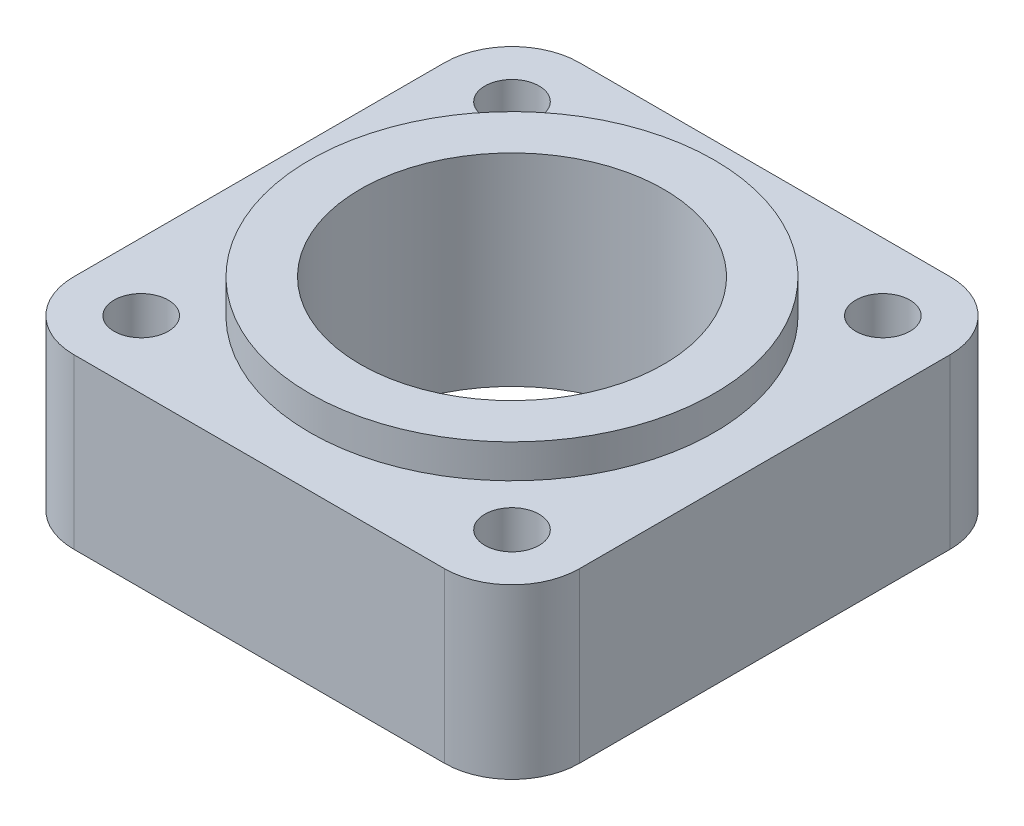
SolidWorks part; units mm, degrees
material "6061-T6 (SS)"
ref_plane "Front Plane" through (0, 0, 0) normal (0, 0, 1) x (1, 0, 0)
ref_plane "Top Plane" through (0, 0, 0) normal (0, 1, 0) x (1, 0, 0)
ref_plane "Right Plane" through (0, 0, 0) normal (1, 0, 0) x (0, 0, -1)
sketch "Sketch1" plane through (0, 0, 0) normal (0, 1, 0) x (1, 0, 0)
  line L1 (23.8125, -23.8125) -> (-23.8125, -23.8125)
  line L2 (23.8125, -23.8125) -> (23.8125, 23.8125)
  line L3 (23.8125, 23.8125) -> (-23.8125, 23.8125)
  line L4 (-23.8125, -23.8125) -> (-23.8125, 23.8125)
  line L5 (23.8125, -23.8125) -> (-23.8125, 23.8125) construction
  line L6 (23.8125, 23.8125) -> (-23.8125, -23.8125) construction
  point P0 (0, 0)
  dimension "D1" = 47.625
extrude "Boss-Extrude1" add sketch "Sketch1" along normal blind 15.875
sketch "Sketch2" plane through (0, 15.875, 0) normal (0, 1, 0) x (1, 0, 0)
  circle A0 centre (0, 0) radius 19.05
  dimension "D1" = 38.1
extrude "Boss-Extrude2" add sketch "Sketch2" along normal blind 3.175
sketch "Sketch3" plane through (0, 19.05, 0) normal (0, 1, 0) x (1, 0, 0)
  circle A0 centre (0, 0) radius 14.2875
  dimension "D1" = 28.575
extrude "Cut-Extrude1" cut sketch "Sketch3" against normal through all
hole_wizard "1/4-20 Tapped Hole1" positions "Sketch4" profile "Sketch5" tap size "1/4-20" standard "ANSI Inch" end condition through all
sketch "Sketch4" plane through (0, 15.875, 0) normal (0, 1, 0) x (1, 0, 0)
  line L0 (-23.8125, 23.8125) -> (23.8125, -23.8125) construction
  line L2 (-23.8125, -23.8125) -> (23.8125, 23.8125) construction
  point P0 (-17.4625, 17.4625)
  point P2 (17.4625, 17.4625)
  point P4 (17.4625, -17.4625)
  point P6 (-17.4625, -17.4625)
  dimension "D1" = 34.925
sketch "Sketch5" plane through (-17.4625, 15.875, -17.4625) normal (1, 0, 0) x (0, 0, 1)
  line L0 (0, 0) -> (0, 15.875)
  line L1 (0, 15.875) -> (2.5527, 15.875)
  line L2 (2.5527, 15.875) -> (2.5527, 0)
  line L5 (2.5527, 0) -> (0, 0)
  line L11 (0, -6.35) -> (0, 107.95) construction
  dimension "Thru Tap Drill Dia." = 5.1054
  dimension "Thru Tap Drill Depth" = 15.875
cosmetic thread "Hole Thread1" parameters "D2"=6.35
cosmetic thread "Hole Thread2" parameters "D2"=6.35
cosmetic thread "Hole Thread3" parameters "D2"=6.35
cosmetic thread "Hole Thread4" parameters "D2"=6.35
fillet "Fillet1" radius 6.35 4 edges at (-23.8125, 7.9375, -23.8125) (23.8125, 7.9375, -23.8125) (-23.8125, 7.9375, 23.8125) (23.8125, 7.9375, 23.8125)
sketch "Sketch6" plane through (0, 0, 0) normal (0, -1, 0) x (1, 0, 0)
  circle A0 centre (0, 0) radius 17.4625
  dimension "D1" = 34.925
extrude "Cut-Extrude2" [suppressed] cut sketch "Sketch6" against normal blind 6.35 flip side to cut
